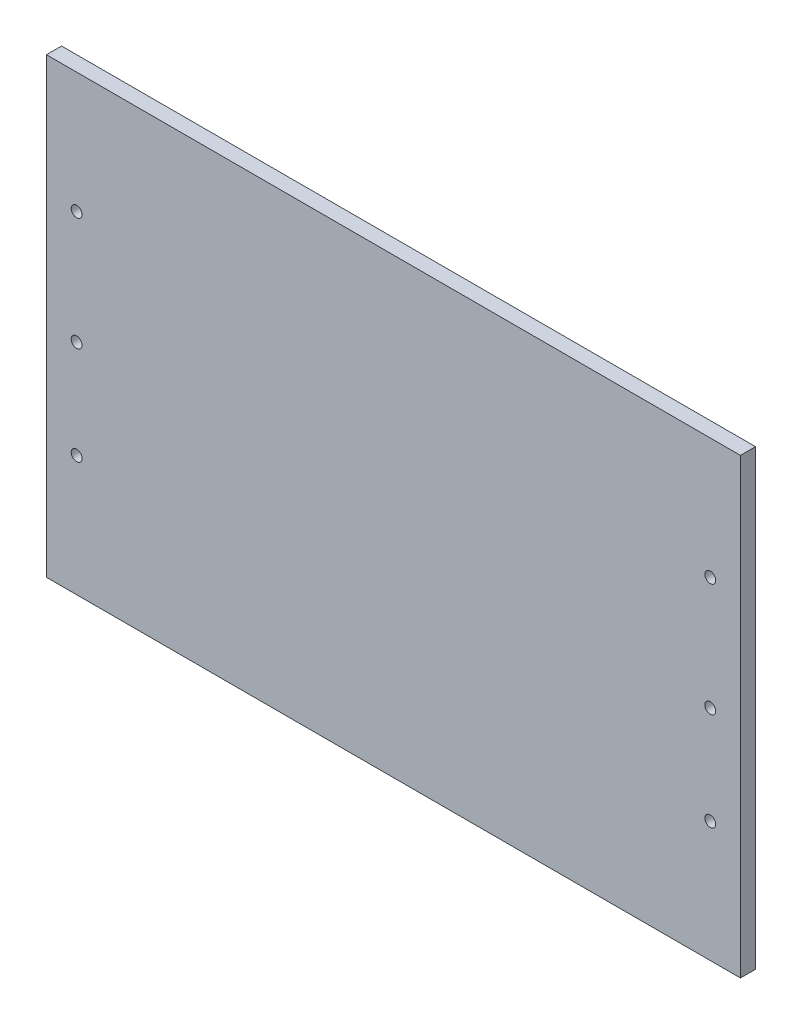
SolidWorks part; units mm, degrees
ref_plane "Płaszczyzna przednia" through (0, 0, 0) normal (0, 0, 1) x (1, 0, 0)
ref_plane "Płaszczyzna górna" through (0, 0, 0) normal (0, 1, 0) x (1, 0, 0)
ref_plane "Płaszczyzna prawa" through (0, 0, 0) normal (1, 0, 0) x (0, 0, -1)
sketch "Szkic1" plane through (0, 0, 0) normal (0, 0, 1) x (1, 0, 0)
  line L1 (-115, -75) -> (115, -75)
  line L2 (-115, -75) -> (-115, 75)
  line L3 (-115, 75) -> (115, 75)
  line L4 (115, -75) -> (115, 75)
  line L5 (0, 75) -> (0, -75) construction
  line L6 (-115, 0) -> (115, 0) construction
  point P0 (0, 0)
  dimension "D1" = 230
  dimension "D2" = 150
extrude "Dodanie-wyciągnięcie1" add sketch "Szkic1" along normal blind 5
sketch "Szkic3" plane through (0, 0, 0) normal (0, 0, -1) x (-1, 0, 0)
  line L0 (0, 75) -> (0, -75) construction
  line L1 (-115, 75) -> (115, 75) construction
  line L2 (115, -75) -> (-115, -75) construction
  circle A1 centre (105, -35) radius 2 construction
  point P18 (105, -35)
  point P21 (105, -2.5)
  point P24 (105, 35)
  point P28 (-105, 35)
  point P29 (-105, -2.5)
  point P30 (-105, -35)
  point P31 (0, 0)
  point P34 (0, 0)
  point P35 (0, 0)
hole_wizard "Pogłębienie walcowe pod M3 Śrubę z łbem stożkowym ściętym1" positions "Szkic3" profile "Szkic4" counterbore size "M3" standard "DIN"
sketch "Szkic4" plane through (105, -35, 0) normal (1, 0, 0) x (0, 1, 0)
  line L0 (0, 0) -> (0, 7.7815)
  line L1 (0, 7.7815) -> (1.8, 6.7)
  line L2 (1.8, 6.7) -> (1.8, 2.4)
  line L3 (1.8, 2.4) -> (3.5, 2.4)
  line L4 (3.5, 2.4) -> (3.5, 0)
  line L5 (3.5, 0) -> (0, 0)
  line L10 (0, 7.7815) -> (-1.8, 6.7) construction
  line L11 (0, -6.35) -> (0, 107.95) construction
  dimension "Średnica otworu" = 3.6
  dimension "Głębokość otworu" = 6.7
  dimension "Średnica pogłębienia walcowego" = 7
  dimension "Głębokość pogłębienia walcowego" = 2.4
  dimension "Kąt wiertła" = 118
